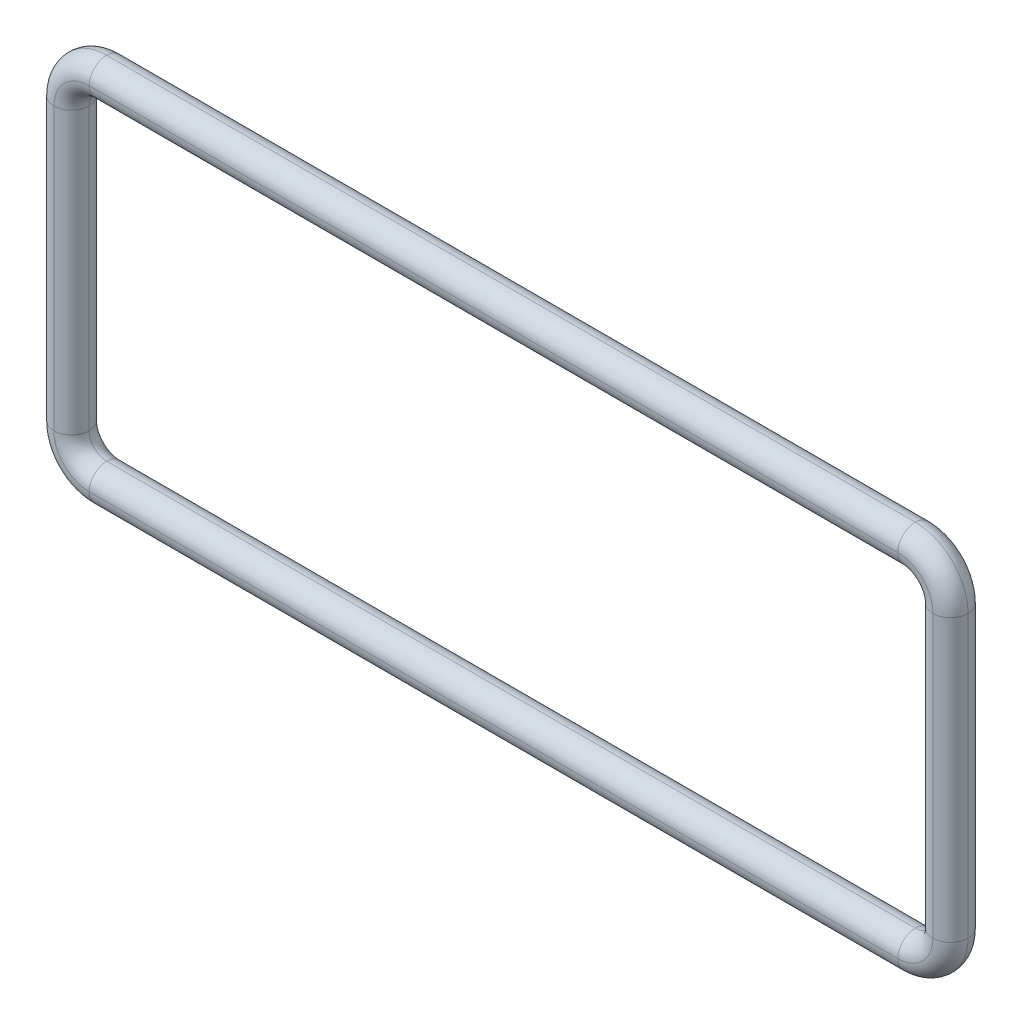
SolidWorks part; units mm, degrees
material "Rubber"
ref_plane "Front Plane" through (0, 0, 0) normal (0, 0, 1) x (1, 0, 0)
ref_plane "Top Plane" through (0, 0, 0) normal (0, 1, 0) x (1, 0, 0)
ref_plane "Right Plane" through (0, 0, 0) normal (1, 0, 0) x (0, 0, -1)
sketch "Sketch1" plane through (0, 0, 0) normal (0, 0, 1) x (1, 0, 0)
  line L0 (50, 18) -> (50, -14)
  line L1 (-44, 20) -> (48, 20)
  line L2 (-46, 18) -> (-46, -14)
  line L3 (-44, -16) -> (48, -16)
  line L5 (54, 18) -> (54, -14)
  line L6 (-44, -20) -> (48, -20)
  line L7 (-50, 18) -> (-50, -14)
  line L8 (-44, 24) -> (48, 24)
  arc A0 (48, 20) -> (50, 18) centre (48, 18) cw
  arc A1 (-44, 20) -> (-46, 18) centre (-44, 18) ccw
  arc A2 (-46, -14) -> (-44, -16) centre (-44, -14) ccw
  arc A3 (48, -16) -> (50, -14) centre (48, -14) ccw
  arc A4 (48, -20) -> (54, -14) centre (48, -14) ccw
  arc A5 (-50, -14) -> (-44, -20) centre (-44, -14) ccw
  arc A6 (-44, 24) -> (-50, 18) centre (-44, 18) ccw
  arc A7 (48, 24) -> (54, 18) centre (48, 18) cw
  dimension "D2" = 2
  dimension "D1" = 2
  dimension "D5" = 2
  dimension "D6" = 92
  dimension "D4" = 2
  dimension "D3" = 92
  dimension "D7" = 32
  dimension "D8" = 46
  dimension "D9" = 16
  dimension "D10" = 4
extrude "Boss-Extrude1" add sketch "Sketch1" along normal blind 4
fillet "Fillet1" radius 2 16 edges at (-46, 2, 4) (-45.4142, -15.4142, 4) (2, -16, 4) (49.4142, -15.4142, 4) (50, 2, 4) (49.4142, 19.4142, 4) (2, 20, 4) (-45.4142, 19.4142, 4) (54, 2, 4) (52.2426, -18.2426, 4) (2, -20, 4) (-48.2426, -18.2426, 4) (-50, 2, 4) (-48.2426, 22.2426, 4) (2, 24, 4) (52.2426, 22.2426, 4)
fillet "Fillet2" radius 2 16 edges at (49.4142, 19.4142, 0) (50, 2, 0) (49.4142, -15.4142, 0) (2, -16, 0) (-45.4142, -15.4142, 0) (-46, 2, 0) (-45.4142, 19.4142, 0) (2, 20, 0) (2, 24, 0) (-48.2426, 22.2426, 0) (-50, 2, 0) (-48.2426, -18.2426, 0) (2, -20, 0) (52.2426, -18.2426, 0) (54, 2, 0) (52.2426, 22.2426, 0)
